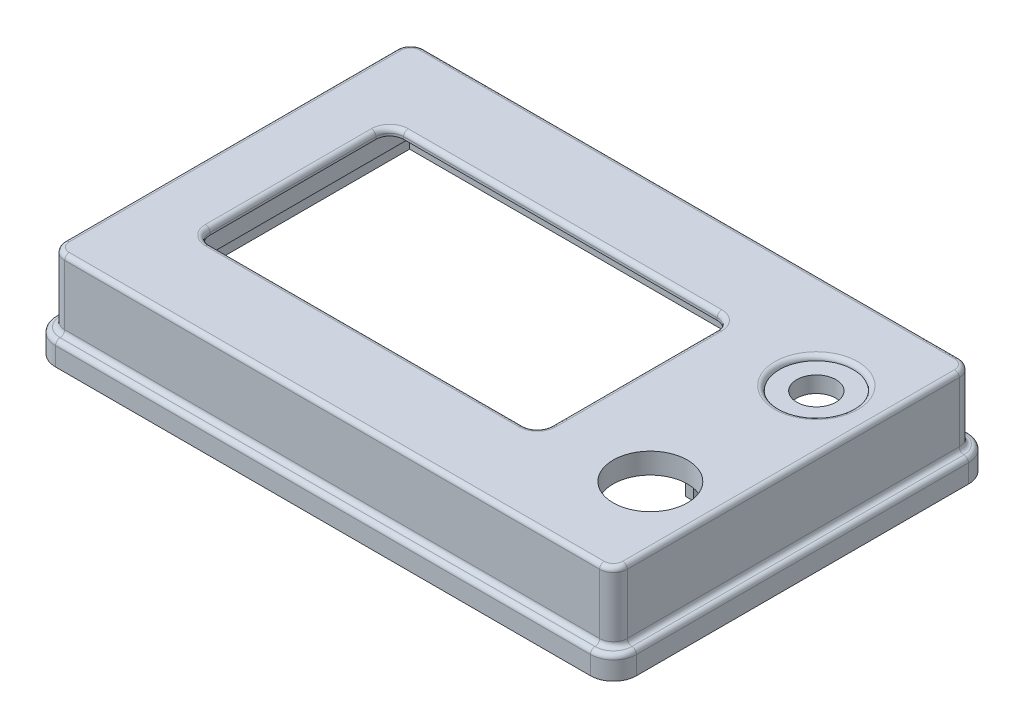
SolidWorks part; units mm, degrees
ref_plane "Front Plane" through (0, 0, 0) normal (0, 0, 1) x (1, 0, 0)
ref_plane "Top Plane" through (0, 0, 0) normal (0, 1, 0) x (1, 0, 0)
ref_plane "Right Plane" through (0, 0, 0) normal (1, 0, 0) x (0, 0, -1)
ref_plane "Plane1" through (0, -3, 0) normal (0, 1, 0) x (1, 0, 0)
sketch "Sketch1" plane through (0, -3, 0) normal (0, 1, 0) x (1, 0, 0)
  line L0 (-48, 36.5) -> (-48, -36.5)
  line L1 (-50.5, 39) -> (71.5, 39)
  line L2 (-50.5, 39) -> (-50.5, -39)
  line L3 (-50.5, -39) -> (71.5, -39)
  line L4 (71.5, 39) -> (71.5, -39)
  line L5 (-48, -36.5) -> (69, -36.5)
  line L6 (69, 36.5) -> (69, -36.5)
  line L7 (-48, 36.5) -> (69, 36.5)
  dimension "D1" = 50.5
  dimension "D2" = 39
  dimension "D3" = 39
  dimension "D4" = 71.5
  dimension "D5" = 2.5
extrude "Boss-Extrude1" add sketch "Sketch1" along normal blind 16
sketch "Sketch2" plane through (0, 13, 0) normal (0, 1, 0) x (1, 0, 0)
  line L0 (71.5, 39) -> (-50.5, 39) construction
  line L1 (71.5, -39) -> (71.5, 39) construction
  line L2 (-50.5, -39) -> (71.5, -39) construction
  line L3 (-50.5, 39) -> (-50.5, -39) construction
  line L4 (71.5, 39) -> (-50.5, 39)
  line L5 (71.5, -39) -> (71.5, 39)
  line L6 (-50.5, -39) -> (71.5, -39)
  line L7 (-50.5, 39) -> (-50.5, -39)
  line L9 (-37, 21) -> (37, 21)
  line L10 (-37, 21) -> (-37, -21)
  line L11 (-37, -21) -> (37, -21)
  line L12 (37, 21) -> (37, -21)
  dimension "D1" = 37
  dimension "D2" = 37
  dimension "D3" = 21
  dimension "D4" = 21
extrude "Boss-Extrude2" add sketch "Sketch2" against normal blind 2.5
sketch "Sketch3" plane through (0, 10.5, 0) normal (0, -1, 0) x (1, 0, 0)
  line L8 (40, -24) -> (40, 24)
  line L9 (-40, -24) -> (40, -24)
  line L10 (-40, 24) -> (-40, -24)
  line L11 (40, 24) -> (-40, 24)
  line L12 (40, -24) -> (40, 24)
  line L13 (-40, -24) -> (40, -24)
  line L14 (-40, 24) -> (-40, -24)
  line L15 (40, 24) -> (-40, 24)
  dimension "D1" = 3
extrude "Cut-Extrude1" cut sketch "Sketch3" against normal blind 1
fillet "Fillet1" radius 3 4 edges at (-50.5, 5, -39) (-50.5, 5, 39) (71.5, 5, -39) (71.5, 5, 39)
sketch "Sketch4" plane through (0, 13, 0) normal (0, 1, 0) x (1, 0, 0)
  line L0 (58.5, 29.1291) -> (58.5, -49.4431) construction
  circle A0 centre (58.5, 18) radius 4.25
  circle A1 centre (58.5, -18) radius 8.05
  dimension "D3" = 8.5
  dimension "D5" = 16.1
  dimension "D1" = 58.5
  dimension "D2" = 18
  dimension "D4" = 18
extrude "Cut-Extrude2" cut sketch "Sketch4" against normal through all
sketch "Sketch5" plane through (0, 10.5, 0) normal (0, -1, 0) x (1, 0, 0)
  line L0 (-48, 36.5) -> (69, 36.5) construction
  line L1 (69, 36.5) -> (69, -36.5) construction
  line L2 (48.5, 36.5) -> (48.5, -36.5)
  line L3 (69, -36.5) -> (-48, -36.5) construction
  line L4 (48.5, -36.5) -> (69, -36.5)
  line L5 (69, -36.5) -> (69, 36.5)
  line L6 (48.5, 36.5) -> (69, 36.5)
  circle A0 centre (58.5, 18) radius 8.05 construction
  circle A1 centre (58.5, -18) radius 4.25 construction
  circle A2 centre (58.5, -18) radius 4.25
  circle A3 centre (58.5, 18) radius 8.05
  dimension "D1" = 20.5
extrude "Boss-Extrude3" add sketch "Sketch5" along normal blind 2
sketch "Sketch6" plane through (0, 13, 0) normal (0, 1, 0) x (1, 0, 0)
  circle A0 centre (58.5, 18) radius 8
  dimension "D1" = 16
extrude "Cut-Extrude3" cut sketch "Sketch6" against normal blind 1
fillet "Fillet2" radius 3 4 edges at (37, 12.25, 21) (-37, 12.25, 21) (-37, 12.25, -21) (37, 12.25, -21)
sketch "Sketch7" plane through (0, 8.5, 0) normal (0, -1, 0) x (1, 0, 0)
  line L0 (57.6433, 9.5) -> (59.3567, 9.5)
  line L1 (59.3567, 9.5) -> (59.3567, 7.5)
  line L2 (59.3567, 7.5) -> (57.6433, 7.5)
  line L3 (57.6433, 7.5) -> (57.6433, 9.5)
  line L4 (58.5, 4.8795) -> (58.5, 19.1184) construction
  line L5 (69, 36.5) -> (69, -36.5) construction
  line L6 (83.8148, 0) -> (-25.5492, 0) construction
  dimension "D1" = 10.5
  dimension "D2" = 9.5
  dimension "D3" = 2
extrude "Boss-Extrude4" add sketch "Sketch7" along normal blind 3
sketch "Sketch8" plane through (57.6433, 0, 0) normal (-1, 0, 0) x (0, 0, 1)
  line L0 (7.5, 5.5) -> (0.4867, 8.5)
  line L1 (36.5, 8.5) -> (-36.5, 8.5) construction
  line L2 (0.4867, 8.5) -> (7.5, 8.5)
  line L3 (7.5, 8.5) -> (7.5, 5.5)
extrude "Boss-Extrude5" add sketch "Sketch8" against normal up to surface (1.7135 mm away) up to face at (59.3567, 7, 8.5)
fillet "Fillet3" radius 1 8 edges at (70.6213, 13, -38.1213) (71.5, 13, 0) (70.6213, 13, 38.1213) (10.5, 13, 39) (-49.6213, 13, 38.1213) (-50.5, 13, 0) (-49.6213, 13, -38.1213) (10.5, 13, -39)
fillet "Fillet4" radius 1 8 edges at (36.1213, 13, -20.1213) (37, 13, 0) (36.1213, 13, 20.1213) (0, 13, 21) (-36.1213, 13, 20.1213) (-37, 13, 0) (-36.1213, 13, -20.1213) (0, 13, -21)
fillet "Fillet5" radius 1 1 edges at (58.5, 13, -10)
sketch "Sketch9" plane through (0, -3, 0) normal (0, -1, 0) x (1, 0, 0)
  line L0 (-47.5, 39) -> (68.5, 39) construction
  line L1 (71.5, 36) -> (71.5, -36) construction
  line L2 (68.5, -39) -> (-47.5, -39) construction
  line L3 (-50.5, -36) -> (-50.5, 36) construction
  line L4 (-47.5, 39) -> (68.5, 39) construction
  line L5 (71.5, 36) -> (71.5, -36) construction
  line L6 (68.5, -39) -> (-47.5, -39) construction
  line L7 (-50.5, -36) -> (-50.5, 36) construction
  line L8 (-52.5, -36) -> (-52.5, 36)
  line L9 (68.5, -41) -> (-47.5, -41)
  line L10 (73.5, 36) -> (73.5, -36)
  line L11 (-47.5, 41) -> (68.5, 41)
  line L13 (-48, 38.3) -> (69, 38.3)
  line L14 (-50, 36.3) -> (-50, -36.3)
  line L15 (-48, -38.3) -> (69, -38.3)
  line L16 (71, 36.3) -> (71, -36.3)
  arc A0 (-47.5, 39) -> (-50.5, 36) centre (-47.5, 36) ccw construction
  arc A1 (71.5, 36) -> (68.5, 39) centre (68.5, 36) ccw construction
  arc A2 (68.5, -39) -> (71.5, -36) centre (68.5, -36) ccw construction
  arc A3 (-50.5, -36) -> (-47.5, -39) centre (-47.5, -36) ccw construction
  arc A4 (-47.5, 39) -> (-50.5, 36) centre (-47.5, 36) ccw construction
  arc A5 (71.5, 36) -> (68.5, 39) centre (68.5, 36) ccw construction
  arc A6 (68.5, -39) -> (71.5, -36) centre (68.5, -36) ccw construction
  arc A7 (-50.5, -36) -> (-47.5, -39) centre (-47.5, -36) ccw construction
  arc A8 (-47.5, 41) -> (-52.5, 36) centre (-47.5, 36) ccw
  arc A9 (-52.5, -36) -> (-47.5, -41) centre (-47.5, -36) ccw
  arc A10 (68.5, -41) -> (73.5, -36) centre (68.5, -36) ccw
  arc A11 (73.5, 36) -> (68.5, 41) centre (68.5, 36) ccw
  arc A12 (-50, -36.3) -> (-48, -38.3) centre (-48, -36.3) ccw
  arc A13 (69, -38.3) -> (71, -36.3) centre (69, -36.3) ccw
  arc A14 (69, 38.3) -> (71, 36.3) centre (69, 36.3) cw
  arc A15 (-48, 38.3) -> (-50, 36.3) centre (-48, 36.3) ccw
  dimension "D6" = 2
  dimension "D2" = 71
  dimension "D3" = 50
  dimension "D4" = 38.3
  dimension "D5" = 38.3
  dimension "D1" = 2
extrude "Boss-Extrude6" add sketch "Sketch9" along normal blind 4 and the other way blind 1
sketch "Sketch10" plane through (0, -3, 0) normal (0, -1, 0) x (1, 0, 0)
  line L0 (69, 38.3) -> (-48, 38.3) construction
  line L1 (-50, 38.3) -> (71, 38.3)
  line L2 (-50, 38.3) -> (-50, -38.3)
  line L3 (-50, -38.3) -> (71, -38.3)
  line L4 (71, 38.3) -> (71, -38.3)
  line L5 (69, -38.3) -> (-48, -38.3) construction
  line L6 (-50, 36.3) -> (-50, -36.3) construction
  line L7 (71, 36.3) -> (71, -36.3) construction
extrude "Cut-Extrude4" cut sketch "Sketch10" along normal through all
fillet "Fillet10" radius 1 16 edges at (-51.0355, -2, 39.5355) (10.5, -2, 41) (72.0355, -2, 39.5355) (73.5, -2, 0) (72.0355, -2, -39.5355) (10.5, -2, -41) (-51.0355, -2, -39.5355) (-49.6213, -2, 38.1213) (10.5, -2, 39) (70.6213, -2, 38.1213) (71.5, -2, 0) (70.6213, -2, -38.1213) (10.5, -2, -39) (-49.6213, -2, -38.1213) (-52.5, -2, 0) (-50.5, -2, 0)
